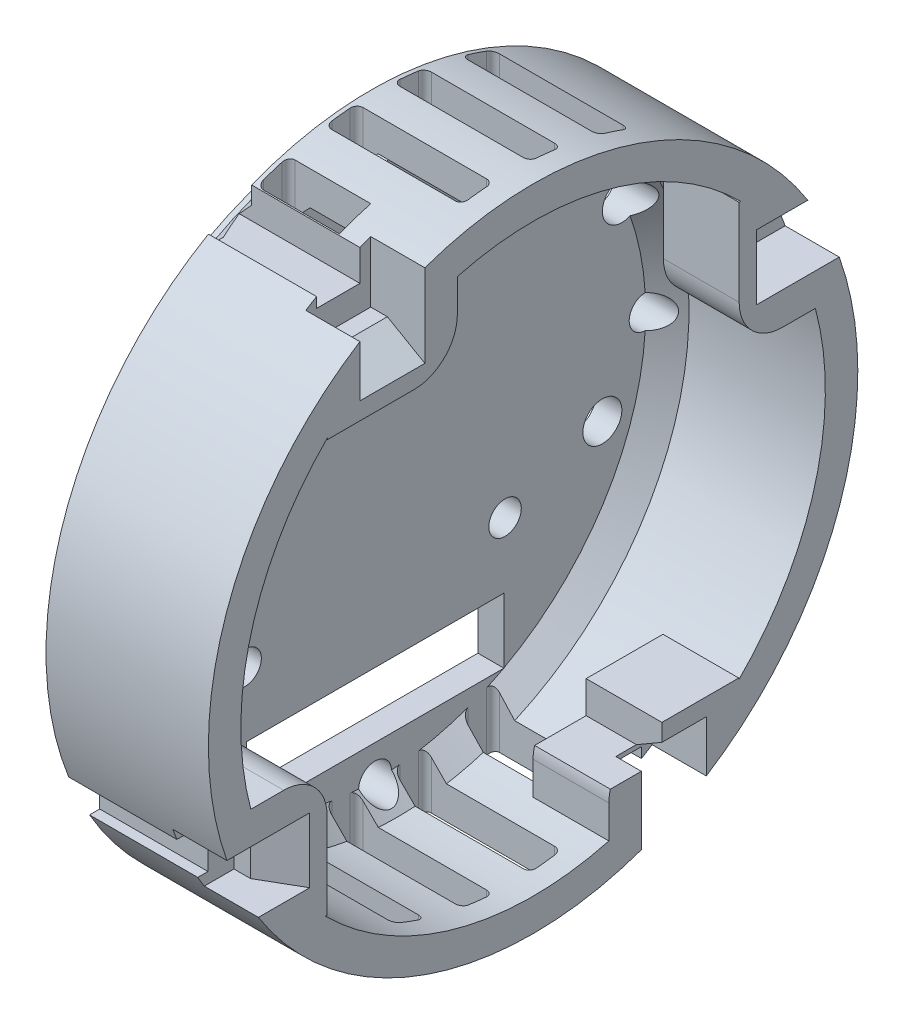
SolidWorks part; units mm, degrees
material "ABS"
ref_plane "Front Plane" through (0, 0, 0) normal (1, 0, 0) x (0, 1, 0)
ref_plane "Top Plane" through (0, 0, 0) normal (0, 0, 1) x (0, 1, 0)
ref_plane "Right Plane" through (0, 0, 0) normal (0, 1, 0) x (-1, 0, 0)
sketch "Sketch1" plane through (0, 0, 0) normal (1, 0, 0) x (0, 1, 0)
  circle A0 centre (0, 0) radius 34.29
  dimension "D1" = 68.58
extrude "Boss-Extrude1" add sketch "Sketch1" along normal blind 2.54
sketch "Sketch2" plane through (2.54, 0, 0) normal (1, 0, 0) x (0, 1, 0)
  circle A0 centre (0, 0) radius 38.1
  dimension "D1" = 76.2
extrude "Boss-Extrude2" add sketch "Sketch2" along normal blind 0.508
sketch "Sketch3" plane through (3.048, 0, 0) normal (1, 0, 0) x (0, 1, 0)
  circle A1 centre (0, 0) radius 38.1
  circle A2 centre (0, 0) radius 34.29
  dimension "D1" = 76.2
  dimension "D2" = 68.58
extrude "Boss-Extrude3" add sketch "Sketch3" along normal blind 18.542
sketch "Sketch5" plane through (3.048, 0, 0) normal (1, 0, 0) x (0, 1, 0)
  circle A0 centre (17.79, 15.25) radius 1.905
  circle A4 centre (17.79, -15.25) radius 1.905
  circle A5 centre (-12.71, -15.25) radius 1.905
  circle A6 centre (-12.71, 15.25) radius 1.905
  point P11 (2.54, 0)
  dimension "D1" = 3.81
  dimension "D2" = 17.79
  dimension "D3" = 15.25
  dimension "D4" = 4
  dimension "D5" = 2.54
extrude "Cut-Extrude1" cut sketch "Sketch5" against normal through all
sketch "Sketch6" plane through (3.048, 0, 0) normal (1, 0, 0) x (0, 1, 0)
  circle A0 centre (28.956, 12.7) radius 2.286
  circle A5 centre (12.7, -28.956) radius 2.286
  circle A7 centre (-12.7, 28.956) radius 2.286
  circle A8 centre (-28.956, -12.7) radius 2.286 [skipped]
  point P12 (0, 0)
  dimension "D2" = 4.572
  dimension "D1" = 12.7
  dimension "D4" = 4
  dimension "D3" = 28.956
extrude "Cut-Extrude10" cut sketch "Sketch6" against normal through all
chamfer "Chamfer2" distance 2.54 angle 45 1 edges at (3.048, 0, -34.29)
sketch "Sketch7" plane through (3.048, 0, 0) normal (1, 0, 0) x (0, 1, 0)
  line L1 (7.9351, 20.32) -> (20.6351, 20.32)
  line L2 (7.9351, 20.32) -> (7.9351, 24.13)
  line L3 (7.9351, 24.13) -> (20.6351, 24.13)
  line L4 (20.6351, 20.32) -> (20.6351, 24.13)
  arc A0 (28.0829, 14.8127) -> (-10.6267, 29.9188) centre (0, 0) ccw construction
  dimension "D1" = 3.81
  dimension "D2" = 12.7
  dimension "D3" = 20.32
extrude "Cut-Extrude11" cut sketch "Sketch7" against normal through all
chamfer "Chamfer3" distance 1.905 angle 45 1 edges at (2.54, 0, -34.29)
sketch "Sketch8" plane through (3.048, 0, 0) normal (1, 0, 0) x (0, 1, 0)
  circle A0 centre (0, -31.75) radius 1.9304
  circle A1 centre (-31.75, 0) radius 1.9304
  circle A2 centre (0, 31.75) radius 1.9304
  circle A3 centre (31.75, 0) radius 1.9304
  point P9 (0, 0)
  dimension "D2" = 3.8608
  dimension "D1" = 31.75
  dimension "D3" = 4
extrude "Cut-Extrude12" cut sketch "Sketch8" against normal through all both and the other way through all
sketch "Sketch9" plane through (3.048, 0, 0) normal (1, 0, 0) x (0, 1, 0)
  line L1 (-27.94, -15.113) -> (-20.32, -15.113)
  line L2 (-27.94, -15.113) -> (-27.94, 15.113)
  line L3 (-27.94, 15.113) -> (-20.32, 15.113)
  line L4 (-20.32, -15.113) -> (-20.32, 15.113)
  line L5 (-27.94, -15.113) -> (-20.32, 15.113) construction
  line L6 (-27.94, 15.113) -> (-20.32, -15.113) construction
  arc A0 (-31.6913, -1.9295) -> (-31.6913, 1.9295) centre (-31.75, 0) ccw construction
  point P0 (-24.13, 0)
  dimension "D3" = 3.81
  dimension "D1" = 7.62
  dimension "D2" = 30.226
extrude "Cut-Extrude13" cut sketch "Sketch9" against normal through all both and the other way through all
sketch "Sketch10" plane through (3.048, 0, 0) normal (1, 0, 0) x (0, 0, -1)
  circle A0 centre (26.67, -8.636) radius 2.286
  arc A1 (31.6913, 1.9295) -> (31.6913, -1.9295) centre (31.75, 0) ccw construction
  dimension "D1" = 4.572
  dimension "D2" = 8.636
  dimension "D3" = 5.08
extrude "Cut-Extrude14" cut sketch "Sketch10" against normal through all both and the other way through all
sketch "Sketch11" plane through (0, -27.94, 0) normal (0, 1, 0) x (-1, 0, 0)
  line L0 (-19.05, 10.16) -> (-19.05, 5.842) construction
  line L1 (-3.81, 13.843) -> (-18.288, 13.843)
  line L2 (-3.048, 13.081) -> (-3.048, 10.922)
  line L3 (-3.81, 10.16) -> (-18.288, 10.16)
  line L4 (-19.05, 13.081) -> (-19.05, 10.922)
  line L5 (-3.81, 5.842) -> (-18.288, 5.842)
  line L6 (-3.048, 5.08) -> (-3.048, 2.921)
  line L7 (-3.81, 2.159) -> (-18.288, 2.159)
  line L8 (-19.05, 5.08) -> (-19.05, 2.921)
  line L9 (-3.81, -2.159) -> (-18.288, -2.159)
  line L10 (-3.048, -2.921) -> (-3.048, -5.08)
  line L11 (-3.81, -5.842) -> (-18.288, -5.842)
  line L12 (-19.05, -2.921) -> (-19.05, -5.08)
  line L13 (-3.81, -10.16) -> (-18.288, -10.16)
  line L14 (-3.048, -10.922) -> (-3.048, -13.081)
  line L15 (-3.81, -13.843) -> (-18.288, -13.843)
  line L16 (-19.05, -10.922) -> (-19.05, -13.081)
  line L17 (-19.05, 2.159) -> (-19.05, -2.159) construction
  line L18 (-19.05, -5.842) -> (-19.05, -10.16) construction
  line L19 (0, 15.113) -> (-3.0635, 15.113) construction
  line L20 (0, -15.113) -> (-3.0635, -15.113) construction
  line L21 (-3.048, 15.0804) -> (-3.048, -15.0804) construction
  line L22 (-21.59, 34.29) -> (-21.59, -34.29) construction
  arc A0 (-3.81, 5.842) -> (-3.048, 5.08) centre (-3.81, 5.08) cw
  arc A1 (-3.048, 2.921) -> (-3.81, 2.159) centre (-3.81, 2.921) cw
  arc A2 (-3.81, -2.159) -> (-3.048, -2.921) centre (-3.81, -2.921) cw
  arc A3 (-3.048, -5.08) -> (-3.81, -5.842) centre (-3.81, -5.08) cw
  arc A4 (-3.81, -10.16) -> (-3.048, -10.922) centre (-3.81, -10.922) cw
  arc A5 (-3.048, -13.081) -> (-3.81, -13.843) centre (-3.81, -13.081) cw
  arc A6 (-18.288, -13.843) -> (-19.05, -13.081) centre (-18.288, -13.081) cw
  arc A7 (-18.288, -10.16) -> (-19.05, -10.922) centre (-18.288, -10.922) ccw
  arc A8 (-18.288, -5.842) -> (-19.05, -5.08) centre (-18.288, -5.08) cw
  arc A9 (-18.288, -2.159) -> (-19.05, -2.921) centre (-18.288, -2.921) ccw
  arc A10 (-18.288, 2.159) -> (-19.05, 2.921) centre (-18.288, 2.921) cw
  arc A11 (-18.288, 5.842) -> (-19.05, 5.08) centre (-18.288, 5.08) ccw
  arc A12 (-18.288, 10.16) -> (-19.05, 10.922) centre (-18.288, 10.922) cw
  arc A13 (-18.288, 13.843) -> (-19.05, 13.081) centre (-18.288, 13.081) ccw
  arc A14 (-3.048, 10.922) -> (-3.81, 10.16) centre (-3.81, 10.922) cw
  arc A15 (-3.81, 13.843) -> (-3.048, 13.081) centre (-3.81, 13.081) cw
  dimension "D4" = 0.762
  dimension "D1" = 1.27
  dimension "D2" = 1.27
  dimension "D3" = 2.54
  dimension "D5" = 4.318
extrude "Cut-Extrude15" cut sketch "Sketch11" against normal through all both and the other way through all
sketch "Sketch12" plane through (0, 0, 0) normal (-1, 0, 0) x (0, -1, 0)
  line L0 (31.797, -13.97) -> (36.877, -13.97)
  line L1 (13.97, 31.797) -> (19.05, 31.797)
  line L2 (13.97, 31.797) -> (13.97, 36.877)
  line L3 (13.97, 36.877) -> (19.05, 36.877)
  line L4 (19.05, 31.797) -> (19.05, 36.877)
  line L5 (13.97, 31.797) -> (19.05, 36.877) construction
  line L6 (13.97, 36.877) -> (19.05, 31.797) construction
  line L7 (31.797, -13.97) -> (31.797, -19.05)
  line L8 (31.797, -19.05) -> (36.877, -19.05)
  line L9 (36.877, -13.97) -> (36.877, -19.05)
  line L10 (-13.97, -31.797) -> (-13.97, -36.877)
  line L11 (-13.97, -31.797) -> (-19.05, -31.797)
  line L12 (-19.05, -31.797) -> (-19.05, -36.877)
  line L13 (-13.97, -36.877) -> (-19.05, -36.877)
  line L14 (-31.797, 13.97) -> (-36.877, 13.97)
  line L15 (-31.797, 13.97) -> (-31.797, 19.05)
  line L16 (-31.797, 19.05) -> (-36.877, 19.05)
  line L17 (-36.877, 13.97) -> (-36.877, 19.05)
  circle A0 centre (0, 0) radius 38.1 construction
  circle A2 centre (0, 31.75) radius 1.9304 construction
  point P0 (16.51, 34.337)
  point P7 (15.5293, 34.7915)
  point P24 (0, 0)
  dimension "D1" = 13.97
  dimension "D2" = 5.08
  dimension "D3" = 5.08
  dimension "D4" = 4
extrude "Cut-Extrude16" cut sketch "Sketch12" against normal up to next
sketch "Sketch13" plane through (21.59, 0, 0) normal (1, 0, 0) x (0, 1, 0)
  line L0 (31.797, 13.97) -> (31.797, 19.05) construction
  line L1 (43.0664, 24.13) -> (24.177, 24.13) construction
  line L2 (43.0664, 24.13) -> (43.0664, 8.89) construction
  line L3 (43.0664, 8.89) -> (24.177, 8.89) construction
  line L4 (24.177, 24.13) -> (24.177, 8.89) construction
  line L5 (43.0664, 24.13) -> (24.177, 8.89) construction
  line L6 (43.0664, 8.89) -> (24.177, 24.13) construction
  line L7 (35.4464, 13.97) -> (31.797, 13.97) construction
  line L8 (29.4848, 24.13) -> (24.177, 24.13)
  line L9 (24.177, 24.13) -> (24.177, 8.89)
  line L10 (24.177, 8.89) -> (37.0483, 8.89)
  line L11 (8.89, -24.177) -> (8.89, -37.0483)
  line L12 (24.13, -29.4848) -> (24.13, -24.177)
  line L13 (24.13, -24.177) -> (8.89, -24.177)
  line L14 (-24.177, -8.89) -> (-37.0483, -8.89)
  line L15 (-29.4848, -24.13) -> (-24.177, -24.13)
  line L16 (-24.177, -24.13) -> (-24.177, -8.89)
  line L17 (-8.89, 24.177) -> (-8.89, 37.0483)
  line L18 (-24.13, 29.4848) -> (-24.13, 24.177)
  line L19 (-24.13, 24.177) -> (-8.89, 24.177)
  arc A0 (29.4848, 24.13) -> (37.0483, 8.89) centre (0, 0) cw
  arc A3 (19.05, -32.9956) -> (35.4464, 13.97) centre (0, 0) ccw construction
  arc A4 (24.13, -29.4848) -> (8.89, -37.0483) centre (0, 0) cw
  arc A5 (-29.4848, -24.13) -> (-37.0483, -8.89) centre (0, 0) cw
  arc A6 (-24.13, 29.4848) -> (-8.89, 37.0483) centre (0, 0) cw
  point P0 (33.6217, 16.51)
  point P10 (31.797, 16.51)
  point P11 (33.6217, 13.97)
  dimension "D1" = 7.62
  dimension "D2" = 5.08
  dimension "D3" = 4
extrude "Boss-Extrude4" add sketch "Sketch13" against normal blind 8.89
sketch "Sketch14" plane through (21.59, 0, 0) normal (1, 0, 0) x (0, 1, 0)
  line L0 (-8.89, 24.177) -> (-8.89, 33.1175) construction
  line L1 (-12.7, 28.749) -> (-20.32, 28.749)
  line L2 (-12.7, 28.749) -> (-12.7, 41.449)
  line L3 (-12.7, 41.449) -> (-20.32, 41.449)
  line L4 (-20.32, 28.749) -> (-20.32, 41.449)
  line L5 (-24.13, 24.177) -> (-8.89, 24.177) construction
  line L6 (-28.749, -12.7) -> (-41.449, -12.7)
  line L7 (-28.749, -12.7) -> (-28.749, -20.32)
  line L8 (-28.749, -20.32) -> (-41.449, -20.32)
  line L9 (-41.449, -12.7) -> (-41.449, -20.32)
  line L10 (12.7, -28.749) -> (12.7, -41.449)
  line L11 (12.7, -28.749) -> (20.32, -28.749)
  line L12 (20.32, -28.749) -> (20.32, -41.449)
  line L13 (12.7, -41.449) -> (20.32, -41.449)
  line L14 (28.749, 12.7) -> (41.449, 12.7)
  line L15 (28.749, 12.7) -> (28.749, 20.32)
  line L16 (28.749, 20.32) -> (41.449, 20.32)
  line L17 (41.449, 12.7) -> (41.449, 20.32)
  point P23 (0, 0)
  point P30 (-27.987, -8.89)
  dimension "D1" = 3.81
  dimension "D2" = 4.572
  dimension "D3" = 7.62
  dimension "D4" = 12.7
  dimension "D5" = 4
extrude "Cut-Extrude17" cut sketch "Sketch14" against normal blind 6.35
fillet "Fillet1" radius 5.08 4 edges at (17.145, 8.89, -24.177) (17.145, -24.177, -8.89) (17.145, -8.89, 24.177) (17.145, 24.177, 8.89)
sketch "Sketch15" plane through (12.7, 0, 0) normal (-1, 0, 0) x (0, -1, 0)
  line L0 (20.32, 15.113) -> (27.94, 15.113) construction
  line L1 (27.94, -15.113) -> (20.32, -15.113)
  line L2 (27.94, -15.113) -> (27.94, 15.113)
  line L3 (27.94, 15.113) -> (20.32, 15.113)
  line L4 (20.32, -15.113) -> (20.32, 15.113)
  line L5 (20.32, -15.113) -> (20.32, 15.113) construction
  point P5 (20.32, 15.113)
extrude "Cut-Extrude18" cut sketch "Sketch15" against normal through all
sketch "Sketch16" plane through (12.7, 0, 0) normal (-1, 0, 0) x (0, -1, 0)
  line L0 (31.797, -13.97) -> (36.877, -13.97)
  line L1 (13.97, 31.797) -> (19.05, 31.797)
  line L2 (13.97, 31.797) -> (13.97, 36.877)
  line L3 (13.97, 36.877) -> (19.05, 36.877)
  line L4 (19.05, 31.797) -> (19.05, 36.877)
  line L5 (31.797, -13.97) -> (31.797, -19.05)
  line L6 (31.797, -19.05) -> (36.877, -19.05)
  line L7 (36.877, -13.97) -> (36.877, -19.05)
  line L8 (-13.97, -31.797) -> (-13.97, -36.877)
  line L9 (-13.97, -31.797) -> (-19.05, -31.797)
  line L10 (-19.05, -31.797) -> (-19.05, -36.877)
  line L11 (-13.97, -36.877) -> (-19.05, -36.877)
  line L12 (-31.797, 13.97) -> (-36.877, 13.97)
  line L13 (-31.797, 13.97) -> (-31.797, 19.05)
  line L14 (-31.797, 19.05) -> (-36.877, 19.05)
  line L15 (-36.877, 13.97) -> (-36.877, 19.05)
  point P21 (0, 0)
  dimension "D1" = 5.08
  dimension "D2" = 4
extrude "Cut-Extrude19" cut sketch "Sketch16" against normal through all
chamfer "Chamfer5" distance 2.54 angle 60 4 edges at (21.59, -28.749, -16.51) (21.59, 16.51, -28.749) (21.59, 28.749, 16.51) (21.59, -16.51, 28.749) first distance on face at (21.59, -2.5876, -1.1968)
